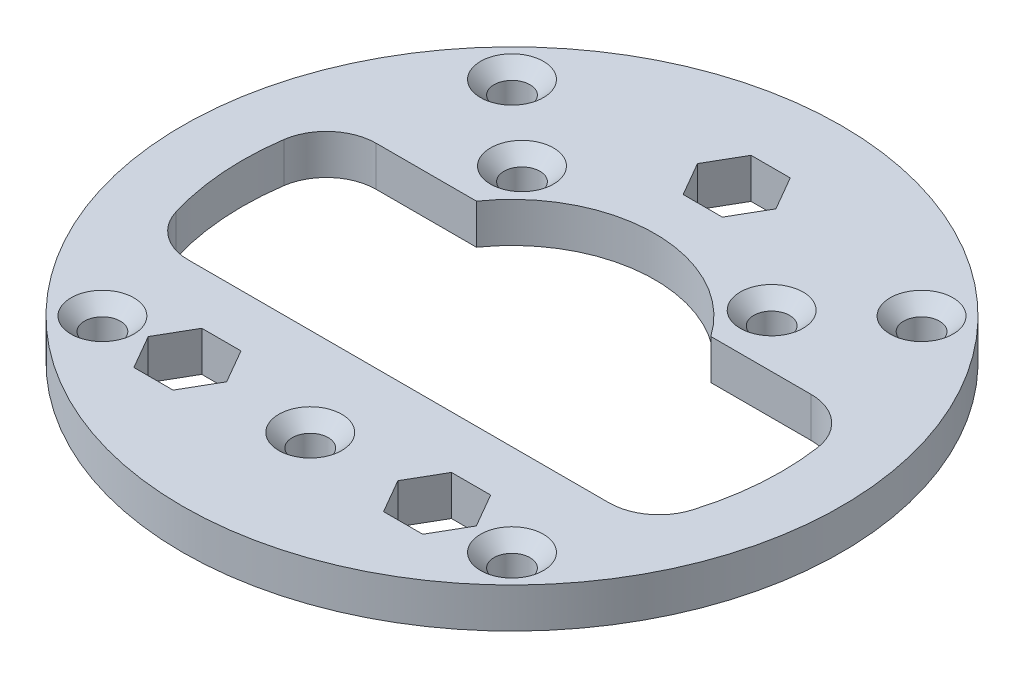
SolidWorks part; units mm, degrees
material "PEI"
ref_plane "Front Plane" through (0, 0, 0) normal (0, 0, 1) x (1, 0, 0)
ref_plane "Top Plane" through (0, 0, 0) normal (0, 1, 0) x (1, 0, 0)
ref_plane "Right Plane" through (0, 0, 0) normal (1, 0, 0) x (0, 0, -1)
sketch "Sketch1" plane through (0, 0, 0) normal (0, 1, 0) x (1, 0, 0)
  circle A0 centre (0, 0) radius 33
  circle A1 centre (0, 0) radius 27
  dimension "D1" = 66
  dimension "D2" = 6
extrude "Boss-Extrude1" add sketch "Sketch1" along normal blind 4
sketch "Sketch2" plane through (0, 4, 0) normal (0, 1, 0) x (1, 0, 0)
  line L0 (-24.5, -11.3468) -> (24.5, -11.3468)
  line L1 (-25.7325, 8.1755) -> (-11.7325, 8.1755)
  line L2 (0, 0) -> (7.7557, 0) construction
  line L3 (11.7325, 8.1755) -> (25.7325, 8.1755)
  line L4 (-20.5061, 20.5061) -> (0, 0) construction
  line L5 (-12.5, 13.5) -> (12.5, 13.5) construction
  circle A0 centre (0, 22.5) radius 2.25 construction
  circle A1 centre (-12.5, -20) radius 2.25 construction
  circle A2 centre (12.5, -20) radius 2.25 construction
  circle A4 centre (-12.5, 13.5) radius 1.5
  circle A6 centre (0, 0) radius 27 construction
  arc A8 (-11.7325, 8.1755) -> (11.7325, 8.1755) centre (0, 0) cw
  arc A9 (25.7325, 8.1755) -> (-25.7325, 8.1755) centre (0, 0) ccw
  arc A10 (24.5, -11.3468) -> (-24.5, -11.3468) centre (0, 0) cw
  circle A11 centre (12.5, 13.5) radius 1.5
  circle A12 centre (0, 0) radius 29 construction
  circle A13 centre (0, 0) radius 33 construction
  circle A14 centre (-20.5061, 20.5061) radius 1.75 construction
  circle A15 centre (20.5061, 20.5061) radius 1.75 construction
  circle A16 centre (20.5061, -20.5061) radius 1.75 construction
  circle A17 centre (-20.5061, -20.5061) radius 1.75 construction
  circle A18 centre (0, -20.2) radius 1.5
  point P15 (0, 13.5)
  point P19 (0, 0)
  point P44 (0, 0)
  circle M2 centre (0, 0) radius 27
  dimension "D5" = 4.5
  dimension "D6" = 4.5
  dimension "D7" = 4.5
  dimension "D12" = 14.3
  dimension "D16" = 3.5
  dimension "D11" = 3
  dimension "D1" = 25
  dimension "D2" = 12.5
  dimension "D3" = 22.5
  dimension "D4" = 20
  dimension "D14" = 4
  dimension "D15" = 135
  dimension "D8" = 14
  dimension "D9" = 14
  dimension "D10" = 49
  dimension "D18" = 25
  dimension "D19" = 20.2
  dimension "D13" = 13.5
  dimension "D17" = 4
extrude "Saliente-Extruir1" add sketch "Sketch2" against normal up to surface (4 mm away) contours L1 A8 L3 M2 | L0 M2 region at (0, 4, 17.7643) region at (0, 4, -16.947) up to face at (0, 0, 33)
sketch "Croquis1" plane through (0, 4, 0) normal (0, 1, 0) x (1, 0, 0)
  line L1 (-8.574, -20) -> (-10.537, -16.6)
  line L2 (-10.537, -16.6) -> (-14.463, -16.6)
  line L3 (-14.463, -16.6) -> (-16.426, -20)
  line L4 (-16.426, -20) -> (-14.463, -23.4)
  line L5 (-14.463, -23.4) -> (-10.537, -23.4)
  line L6 (-10.537, -23.4) -> (-8.574, -20)
  line L7 (16.426, -20) -> (14.463, -16.6)
  line L8 (14.463, -16.6) -> (10.537, -16.6)
  line L9 (10.537, -16.6) -> (8.574, -20)
  line L10 (8.574, -20) -> (10.537, -23.4)
  line L11 (10.537, -23.4) -> (14.463, -23.4)
  line L12 (14.463, -23.4) -> (16.426, -20)
  line L13 (3.926, 22.5) -> (1.963, 25.9)
  line L14 (1.963, 25.9) -> (-1.963, 25.9)
  line L15 (-1.963, 25.9) -> (-3.926, 22.5)
  line L16 (-3.926, 22.5) -> (-1.963, 19.1)
  line L17 (-1.963, 19.1) -> (1.963, 19.1)
  line L18 (1.963, 19.1) -> (3.926, 22.5)
  circle A0 centre (-20.5061, 20.5061) radius 1.75 construction
  circle A1 centre (-20.5061, 20.5061) radius 1.75
  circle A4 centre (20.5061, 20.5061) radius 1.75 construction
  circle A5 centre (20.5061, 20.5061) radius 1.75
  circle A6 centre (-12.5, -20) radius 3.4 construction
  circle A7 centre (12.5, -20) radius 3.4 construction
  circle A8 centre (0, 22.5) radius 3.4 construction
  circle A16 centre (-20.5061, -20.5061) radius 1.75 construction
  circle A17 centre (-20.5061, -20.5061) radius 1.75
  circle A18 centre (20.5061, -20.5061) radius 1.75 construction
  circle A19 centre (20.5061, -20.5061) radius 1.75
  dimension "D1" = 6.8
  dimension "D2" = 6.8
  dimension "D3" = 6.8
extrude "Cortar-Extruir1" cut sketch "Croquis1" against normal up to next
hole_wizard "CSK for M3 Flat Head Machine Screw1" positions "Sketch4" profile "Sketch5" countersink size "M3" standard "ANSI Metric" end condition through all
sketch "Sketch4" plane through (0, 4, 0) normal (0, 1, 0) x (1, 0, 0)
  point P0 (-20.5061, 20.5061)
  point P3 (20.5061, 20.5061)
  point P6 (20.5061, -20.5061)
  point P9 (-20.5061, -20.5061)
sketch "Sketch5" plane through (-20.5061, 4, -20.5061) normal (1, 0, 0) x (0, 0, 1)
  line L0 (0, 0) -> (0, 4)
  line L1 (0, 4) -> (1.8, 4)
  line L2 (1.8, 4) -> (1.8, 1.35)
  line L3 (1.8, 1.35) -> (3.15, 0)
  line L5 (3.15, 0) -> (0, 0)
  line L6 (-1.8, 1.35) -> (-3.15, 0) construction
  line L11 (0, -6.35) -> (0, 107.95) construction
  dimension "Thru Hole Dia." = 3.6
  dimension "Thru Hole Depth" = 4
  dimension "Near C'Sink Dia." = 6.3
  dimension "Near C'Sink Angle" = 90
hole_wizard "CSK for M3 Flat Head Machine Screw2" positions "Sketch6" profile "Sketch7" countersink size "M3" standard "ANSI Metric" end condition through all
sketch "Sketch6" plane through (0, 4, 0) normal (0, 1, 0) x (1, 0, 0)
  point P12 (-12.5, 13.5)
  point P15 (12.5, 13.5)
  point P18 (0, -20.2)
sketch "Sketch7" plane through (-12.5, 4, -13.5) normal (1, 0, 0) x (0, 0, 1)
  line L0 (0, 0) -> (0, 4)
  line L1 (0, 4) -> (1.8, 4)
  line L2 (1.8, 4) -> (1.8, 1.35)
  line L3 (1.8, 1.35) -> (3.15, 0)
  line L5 (3.15, 0) -> (0, 0)
  line L6 (-1.8, 1.35) -> (-3.15, 0) construction
  line L11 (0, -6.35) -> (0, 107.95) construction
  dimension "Thru Hole Dia." = 3.6
  dimension "Thru Hole Depth" = 4
  dimension "Near C'Sink Dia." = 6.3
  dimension "Near C'Sink Angle" = 90
fillet "Fillet1" radius 5 4 edges at (-25.7325, 2, -8.1755) (25.7325, 2, -8.1755) (24.5, 2, 11.3468) (-24.5, 2, 11.3468)
equation "\"D2@Sketch2\"=\"D1@Sketch2\"/2"
equation "\"D6@Sketch2\"=\"D5@Sketch2\""
equation "\"D7@Sketch2\"=\"D6@Sketch2\""
equation "\"D2@Croquis1\"=\"D3@Croquis1\""
equation "\"D1@Croquis1\"=\"D3@Croquis1\""
